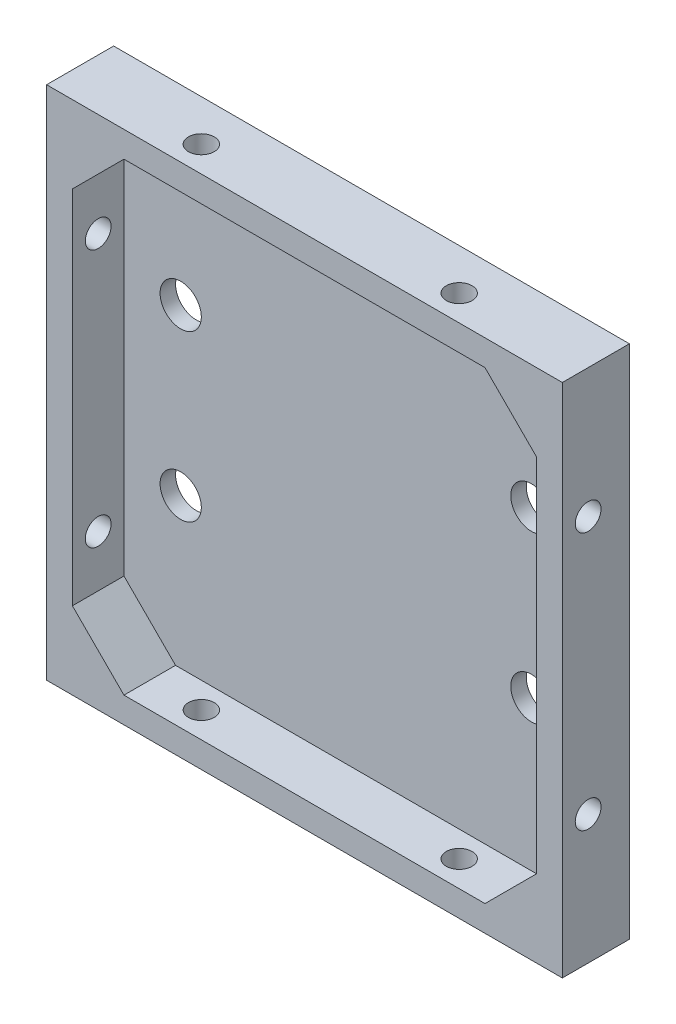
SolidWorks part; units mm, degrees
ref_plane "Plan de face" through (0, 0, 0) normal (0, 0, 1) x (1, 0, 0)
ref_plane "Plan de dessus" through (0, 0, 0) normal (0, 1, 0) x (1, 0, 0)
ref_plane "Plan de droite" through (0, 0, 0) normal (1, 0, 0) x (0, 0, -1)
sketch "Esquisse1" plane through (0, 0, 0) normal (0, 0, 1) x (1, 0, 0)
  line L0 (44.1184, 33.7284) -> (54.1184, 33.7284)
  line L1 (-45.8816, 33.7284) -> (44.1184, 33.7284)
  line L2 (-45.8816, 33.7284) -> (-45.8816, -66.2716)
  line L3 (-45.8816, -66.2716) -> (54.1184, -66.2716)
  line L4 (54.1184, 23.7284) -> (54.1184, -66.2716)
  line L5 (54.1184, 33.7284) -> (54.1184, 23.7284)
  point P6 (54.1184, 33.7284)
  dimension "D1" = 100
  dimension "D2" = 100
extrude "Boss.-Extru.1" add sketch "Esquisse1" along normal blind 13
shell "Coque1" thickness 5 removed face at (4.1184, -16.2716, 13)
sketch "Esquisse2" plane through (-45.8816, 0, 0) normal (-1, 0, 0) x (0, 0, 1)
  line L0 (13, 33.7284) -> (13, -66.2716) construction
  line L1 (13, 33.7284) -> (0, 33.7284) construction
  line L2 (13, -66.2716) -> (0, -66.2716) construction
  circle A0 centre (8, 8.7284) radius 2.5
  circle A1 centre (8, -41.2716) radius 2.5
  dimension "D1" = 5
  dimension "D2" = 5
  dimension "D3" = 5
  dimension "D4" = 5
  dimension "D5" = 25
  dimension "D6" = 25
extrude "Enlèv. mat.-Extru.1" cut sketch "Esquisse2" against normal up to surface (100 mm away) contours A1 | A0 region at (-45.8816, -41.2716, 8) up to face at (54.1184, -16.2716, 6.5)
sketch "Esquisse3" plane through (0, -66.2716, 0) normal (0, -1, 0) x (1, 0, 0)
  line L0 (-45.8816, 13) -> (54.1184, 13) construction
  line L2 (54.1184, 13) -> (54.1184, 0) construction
  line L3 (-45.8816, 13) -> (-45.8816, 0) construction
  circle A0 centre (-20.8816, 8) radius 2.5
  circle A1 centre (29.1184, 8) radius 2.5
  dimension "D1" = 5
  dimension "D2" = 5
  dimension "D3" = 5
  dimension "D4" = 5
  dimension "D5" = 25
  dimension "D6" = 25
extrude "Enlèv. mat.-Extru.2" cut sketch "Esquisse3" against normal up to surface (100 mm away) up to face at (4.1184, 33.7284, 6.5)
sketch "Esquisse4" plane through (0, 0, 3) normal (0, 0, 1) x (1, 0, 0)
  line L0 (-30.8816, 28.7284) -> (-40.8816, 18.7284)
  line L1 (49.1184, 28.7284) -> (-40.8816, 28.7284) construction
  line L2 (-40.8816, 28.7284) -> (-40.8816, -61.2716) construction
  line L3 (-40.8816, 18.7284) -> (-40.8816, 28.7284)
  line L4 (-40.8816, 28.7284) -> (-30.8816, 28.7284)
  line L5 (49.1184, 28.7284) -> (49.1184, 18.7284)
  line L6 (49.1184, -61.2716) -> (49.1184, 28.7284) construction
  line L7 (49.1184, 18.7284) -> (39.1184, 28.7284)
  line L8 (39.1184, 28.7284) -> (49.1184, 28.7284)
  line L9 (49.1184, 28.7284) -> (-40.8816, 28.7284) construction
  line L10 (49.1184, -61.2716) -> (49.1184, -51.2716)
  line L11 (49.1184, -51.2716) -> (39.1184, -61.2716)
  line L12 (-40.8816, -61.2716) -> (49.1184, -61.2716) construction
  line L13 (39.1184, -61.2716) -> (49.1184, -61.2716)
  line L14 (-30.8816, -61.2716) -> (-40.8816, -51.2716)
  line L15 (-40.8816, 28.7284) -> (-40.8816, -61.2716) construction
  line L16 (-40.8816, -51.2716) -> (-40.8816, -61.2716)
  line L17 (-40.8816, -61.2716) -> (-30.8816, -61.2716)
  dimension "D1" = 10
  dimension "D2" = 10
  dimension "D3" = 10
  dimension "D4" = 10
  dimension "D5" = 10
  dimension "D6" = 10
  dimension "D7" = 10
  dimension "D8" = 10
extrude "Boss.-Extru.2" add sketch "Esquisse4" along normal up to surface (10 mm away) up to face at (4.1184, -16.2716, 13)
sketch "Esquisse5" plane through (0, 0, 3) normal (0, 0, 1) x (1, 0, 0)
  line L0 (54.1184, 33.7284) -> (-45.8816, 33.7284) construction
  line L1 (-45.8816, -66.2716) -> (54.1184, -66.2716) construction
  line L2 (-45.8816, 33.7284) -> (-45.8816, -66.2716) construction
  circle A0 centre (-29.8816, -0.2716) radius 4
  circle A1 centre (-29.8816, -32.2716) radius 4
  point P6 (-25.5549, 33.7284)
  dimension "D1" = 8
  dimension "D2" = 8
  dimension "D3" = 32
  dimension "D4" = 34
  dimension "D5" = 34
  dimension "D6" = 16
extrude "Enlèv. mat.-Extru.3" cut sketch "Esquisse5" against normal up to surface (3 mm away) up to face at (4.1184, -16.2716, 0)
pattern_linear "Répétition linéaire1" count 2 spacing 68 along (1, 0, 0) of "Enlèv. mat.-Extru.3"
